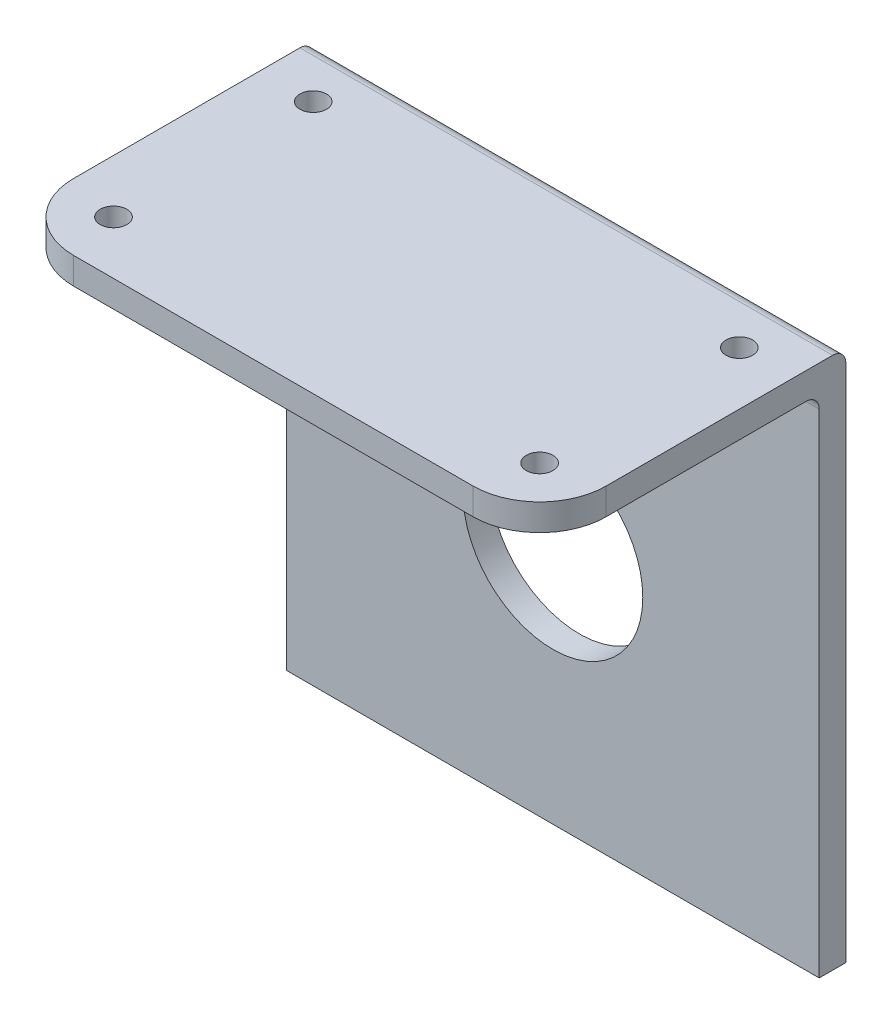
SolidWorks part; units mm, degrees
ref_plane "Front Plane" through (0, 0, 0) normal (0, 0, 1) x (1, 0, 0)
ref_plane "Top Plane" through (0, 0, 0) normal (0, 1, 0) x (1, 0, 0)
ref_plane "Right Plane" through (0, 0, 0) normal (1, 0, 0) x (0, 0, -1)
sketch "Sketch1" plane through (0, 0, 0) normal (0, 0, 1) x (1, 0, 0)
  line L1 (-20, 20) -> (20, 20)
  line L2 (-20, 20) -> (-20, -20)
  line L3 (-20, -20) -> (20, -20)
  line L4 (20, 20) -> (20, -20)
  circle A1 centre (0, -1.8789) radius 6.75
  dimension "D2" = 40
  dimension "D3" = 40
extrude "Boss-Extrude2" add sketch "Sketch1" along normal blind 2
sketch "Sketch2" plane through (0, 0, 0) normal (0, 0, 1) x (1, 0, 0)
  line L0 (20, -20) -> (20, 20) construction
  line L1 (-20, 20) -> (20, 20)
  line L2 (-20, 20) -> (-20, 18)
  line L3 (-20, 18) -> (20, 18)
  line L4 (20, 20) -> (20, 18)
  dimension "D1" = 40
  dimension "D2" = 2
extrude "Boss-Extrude3" add sketch "Sketch2" along normal blind 23
ref_plane "Plane1" through (0, 20, 0) normal (0, 1, 0) x (1, 0, 0)
sketch "Sketch3" plane through (0, 20, 0) normal (0, 1, 0) x (1, 0, 0)
  line L0 (0, -23) -> (0, 0) construction
  line L1 (20, -23) -> (-20, -23) construction
  line L2 (-20, -11.5) -> (20, -11.5) construction
  line L3 (-20, -23) -> (-20, 0) construction
  line L4 (20, -23) -> (20, 0) construction
  line L5 (20, 0) -> (-20, 0) construction
  circle A0 centre (-16, -4) radius 1
  circle A1 centre (16, -4) radius 1
  circle A2 centre (16, -19) radius 1
  circle A3 centre (-16, -19) radius 1
  dimension "D1" = 2
  dimension "D2" = 4
  dimension "D3" = 4
extrude "Cut-Extrude1" cut sketch "Sketch3" against normal up to surface (2 mm away) up to face at (0, 18, 12.5)
fillet "Fillet1" radius 1 1 edges at (0, 20, 0)
fillet "Fillet2" radius 1 1 edges at (0, 18, 2)
fillet "Fillet3" radius 5 2 edges at (20, 19, 23) (-20, 19, 23)
